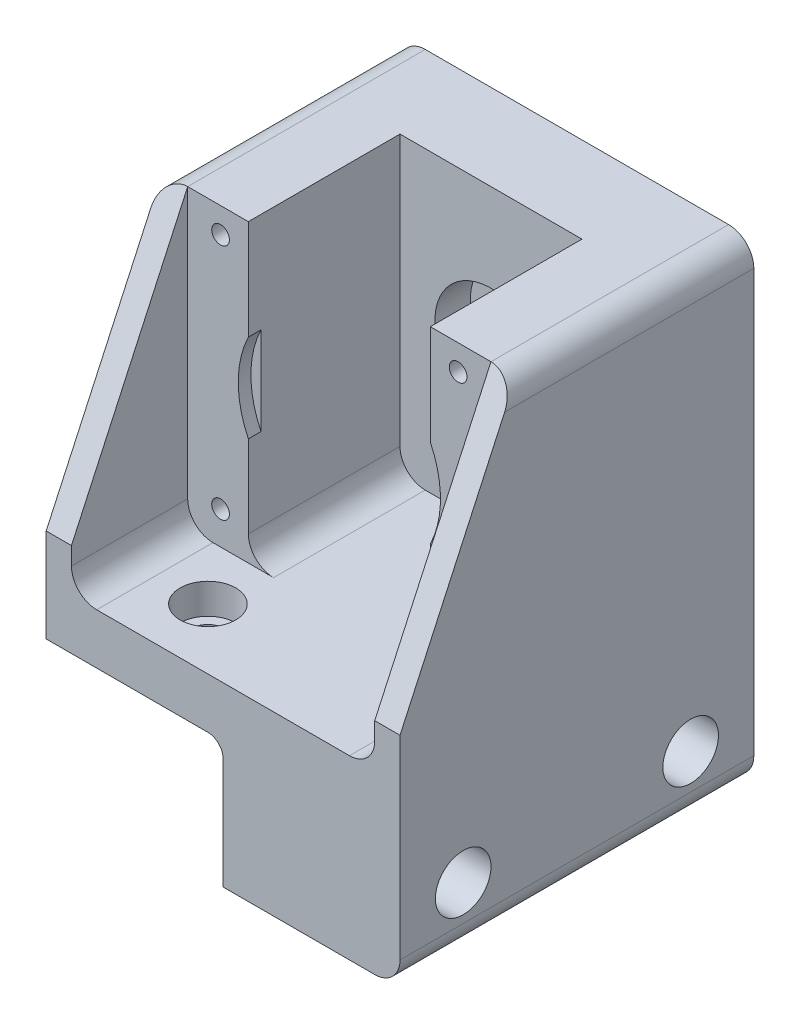
SolidWorks part; units mm, degrees
ref_plane "Front Plane" through (0, 0, 0) normal (0, 0, 1) x (1, 0, 0)
ref_plane "Top Plane" through (0, 0, 0) normal (0, 1, 0) x (1, 0, 0)
ref_plane "Right Plane" through (0, 0, 0) normal (1, 0, 0) x (0, 0, -1)
sketch "Sketch1" plane through (0, 0, 0) normal (0, 0, 1) x (1, 0, 0)
  line L0 (0, 28.5) -> (0, -65) construction
  line L1 (-23.5, -23.5) -> (23.5, -23.5) construction
  line L2 (-23.5, -23.5) -> (-23.5, 23.5) construction
  line L3 (-23.5, 23.5) -> (23.5, 23.5) construction
  line L4 (23.5, -23.5) -> (23.5, 23.5) construction
  line L5 (-23.5, -23.5) -> (23.5, 23.5) construction
  line L6 (-23.5, 23.5) -> (23.5, -23.5) construction
  line L7 (-35, 28.5) -> (35, 28.5)
  line L8 (-35, 28.5) -> (-35, -25)
  line L9 (-35, -65) -> (35, -65)
  line L10 (35, 28.5) -> (35, -25)
  line L11 (-35, -25) -> (-35, -65)
  line L13 (35, -25) -> (35, -65)
  line L14 (-35, -40) -> (-3, -40)
  line L15 (0, -43) -> (0, -65)
  circle A0 centre (0, 0) radius 6
  circle A1 centre (-23.5, 23.5) radius 1.75
  circle A2 centre (23.5, 23.5) radius 1.75
  circle A3 centre (23.5, -23.5) radius 1.75
  circle A4 centre (-23.5, -23.5) radius 1.75
  arc A6 (-3, -40) -> (0, -43) centre (-3, -43) cw
  point P26 (0, -55.45)
  point P27 (-24.9184, -41.7868)
  dimension "D1" = 3.5
  dimension "D3" = 12
  dimension "D8" = 3
  dimension "D2" = 47
  dimension "D4" = 28.5
  dimension "D5" = 70
  dimension "D6" = 70
  dimension "D7" = 35
  dimension "D9" = 40
  dimension "D10" = 40
  dimension "D11" = 25
extrude "Boss-Extrude1" add sketch "Sketch1" against normal blind 70 contours L14 A6 L15 L9 L13 L10 L7 L8 L11 A4 A3 A2 A1 A0 region at (2.7736, -13.3302, 0)
sketch "Sketch2" plane through (0, 0, 0) normal (0, 0, 1) x (1, 0, 0)
  line L0 (-30, 28.5) -> (-30, -30)
  line L1 (-35, 28.5) -> (35, 28.5) construction
  line L2 (-30, -30) -> (30, -30)
  line L3 (30, -30) -> (30, 28.5)
  line L4 (-30, 28.5) -> (30, 28.5)
  line L5 (0, 28.5) -> (0, -30) construction
  line L14 (-35, -40) -> (-3, -40)
  line L15 (0, -43) -> (0, -65)
  line L16 (0, -65) -> (35, -65)
  line L17 (35, -65) -> (35, 28.5)
  line L18 (35, 28.5) -> (-35, 28.5)
  line L19 (-35, 28.5) -> (-35, -40)
  line L26 (30, 28.5) -> (0, 28.5)
  arc A2 (0, -43) -> (-3, -40) centre (-3, -43) ccw
  circle M14 centre (-23.5, -23.5) radius 1.75
  circle M15 centre (23.5, -23.5) radius 1.75
  circle M16 centre (23.5, 23.5) radius 1.75
  circle M17 centre (-23.5, 23.5) radius 1.75
  circle M18 centre (0, 0) radius 6
  line M24 (35, 28.5) -> (-35, 28.5)
  dimension "D1" = 30
  dimension "D2" = 60
  dimension "D3" = 0
extrude "Cut-Extrude2" cut sketch "Sketch2" against normal blind 23 contours L5 L4 L0 L2 M18 M17 M14 | L5 L2 L3 M24 M18 M16 M15 region at (-15.322, -0.7839, 0) region at (15.322, -0.7839, 0)
sketch "Sketch6" plane through (0, 0, 0) normal (0, 0, 1) x (1, 0, 0)
  line L0 (-18, -30) -> (-18, -8.7178)
  line L1 (-30, -30) -> (30, -30) construction
  line L2 (30, 28.5) -> (-30, 28.5) construction
  line L3 (-18, 28.5) -> (18, 28.5)
  line L4 (18, 28.5) -> (18, 8.7178)
  line L5 (18, -30) -> (-18, -30)
  line L6 (0, 0) -> (0, -30) construction
  line L7 (-18, 8.7178) -> (-18, 28.5)
  line L8 (18, -8.7178) -> (18, -30)
  line L9 (-18, 8.7178) -> (-18, -8.7178)
  line L10 (18, 8.7178) -> (18, -8.7178)
  arc A0 (-18, 8.7178) -> (-18, -8.7178) centre (0, 0) ccw
  arc A1 (18, -8.7178) -> (18, 8.7178) centre (0, 0) ccw
  line M7 (30, -30) -> (-30, -30)
  dimension "D2" = 40
  dimension "D1" = 36
extrude "Cut-Extrude3" cut sketch "Sketch6" against normal blind 53 contours L10 L4 L3 L7 L9 L0 L5 L8 M7 region at (0, -0.75, 0)
extrude "Cut-Extrude5" cut sketch "Sketch6<4>" against normal blind 2.5 from surface contours L9 A0 | L10 A1 region at (-18.8035, 0, 0) region at (18.8035, 0, 0) starting at face at (-21.75, -23.5, -23)
sketch "Sketch6<4>" plane through (0, 0, 0) normal (0, 0, 1) x (1, 0, 0) same geometry as "Sketch6"
sketch "Sketch5" plane through (0, 0, -53) normal (0, 0, 1) x (1, 0, 0)
  circle A0 centre (0, 0) radius 11.1
  dimension "D1" = 22.2
extrude "Cut-Extrude4" cut sketch "Sketch5" against normal blind 7
chamfer "Chamfer1" distance 50 distance2 23 2 edges at (32.5, 28.5, 0) (-32.5, 28.5, 0) first distance on face at (-0.2162, -18.0344, 0)
fillet "Fillet1" radius 5 3 edges at (35, -65, -35) (35, 28.5, -46.5) (-35, 28.5, -46.5)
fillet "Fillet2" radius 5 4 edges at (30, -30, -11.5) (18, -30, -38) (-18, -30, -38) (-30, -30, -11.5)
hole_wizard "CBORE for M6 Socket Head Cap Screw1" positions "3DSketch1" profile "Sketch9" counterbore size "M6" standard "IS" end condition through all
sketch3d "3DSketch1"
  point P0 (-15, -30, -12)
  point P38 (0, 0, 0)
  point P39 (0, 0, 0)
  point P40 (0, 0, 0)
  point P41 (0, 0, 0)
  point P42 (41.2882, -53, -34.4305)
  point P43 (0, 0, 0)
  dimension "D4" = 12
  dimension "D5" = 15
sketch "Sketch9" plane through (-15, -30, -12) normal (1, 0, 0) x (0, 0, 1)
  line L0 (0, 0) -> (0, 35)
  line L1 (0, 35) -> (3.5, 35)
  line L3 (3.5, 35) -> (3.5, 6)
  line L4 (3.5, 6) -> (5.5, 6)
  line L5 (5.5, 6) -> (5.5, 0)
  line L7 (5.5, 0) -> (0, 0)
  line L11 (0, -6.35) -> (0, 107.95) construction
  dimension "Thru Hole Dia." = 7
  dimension "Thru Hole Depth" = 35
  dimension "C'Bore Dia." = 11
  dimension "C'Bore Depth" = 6
sketch "Sketch10" plane through (35, 0, 0) normal (1, 0, 0) x (0, 0, -1)
  line L0 (12.5, -53) -> (57.5, -53) construction
  line L2 (35, -65) -> (35, -53) construction
  line L3 (70, -65) -> (0, -65) construction
  point P2 (35, -53)
  dimension "D1" = 12
  dimension "D2" = 45
hole_wizard "CBORE for M6 Socket Head Cap Screw2" positions "Sketch11" profile "Sketch12" counterbore size "M6" standard "IS" end condition through all
sketch "Sketch11" plane through (35, 0, 0) normal (1, 0, 0) x (0, 0, -1)
  point P0 (12.5, -53)
  point P3 (57.5, -53)
sketch "Sketch12" plane through (35, -53, -12.5) normal (0, 1, 0) x (0, 0, -1)
  line L0 (0, 0) -> (0, 70)
  line L1 (0, 70) -> (3.5, 70)
  line L3 (3.5, 70) -> (3.5, 15)
  line L4 (3.5, 15) -> (5.5, 15)
  line L5 (5.5, 15) -> (5.5, 0)
  line L7 (5.5, 0) -> (0, 0)
  line L11 (0, -6.35) -> (0, 107.95) construction
  dimension "Thru Hole Dia." = 7
  dimension "Thru Hole Depth" = 70
  dimension "C'Bore Dia." = 11
  dimension "C'Bore Depth" = 15
chamfer "Chamfer2" distance 1 angle 45 1 edges at (6, 0, -60)
